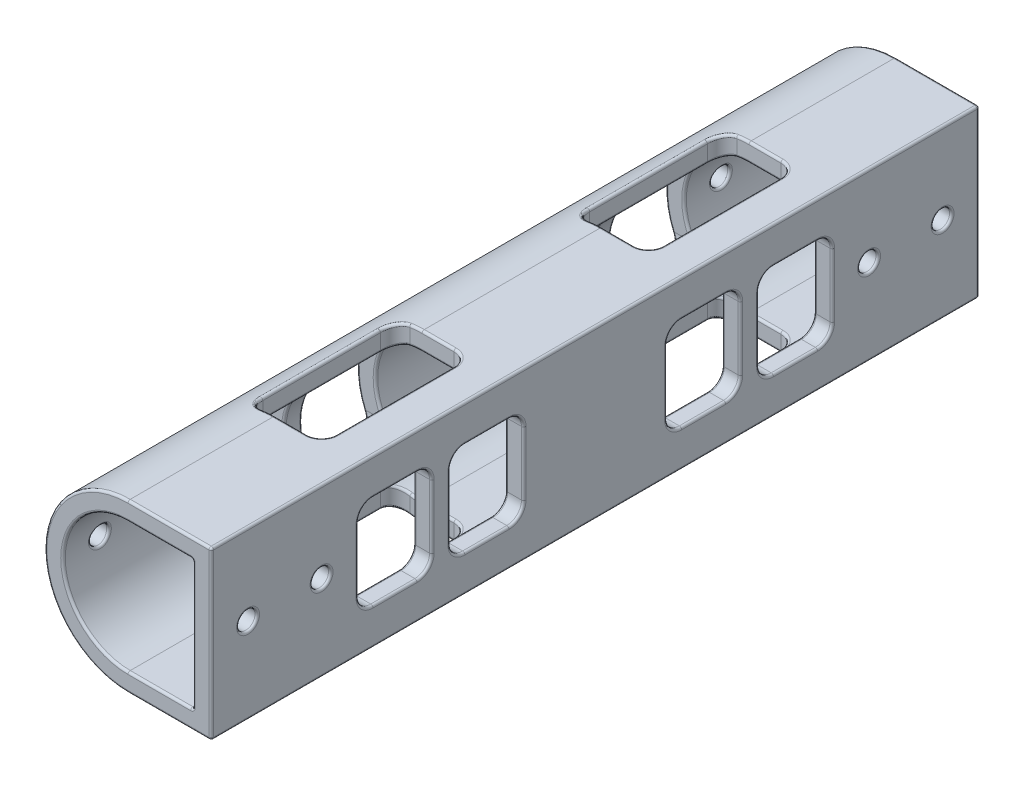
SolidWorks part; units mm, degrees
ref_plane "Front Plane" through (0, 0, 0) normal (0, 0, 1) x (1, 0, 0)
ref_plane "Top Plane" through (0, 0, 0) normal (0, 1, 0) x (1, 0, 0)
ref_plane "Right Plane" through (0, 0, 0) normal (1, 0, 0) x (0, 0, -1)
sketch "Sketch1" plane through (0, 0, 0) normal (0, 0, 1) x (1, 0, 0)
  line L1 (0, 13.9792) -> (14.3954, 13.9792)
  line L2 (0, 13.9792) -> (0, -14.8117)
  line L3 (0, -14.8117) -> (14.3955, -14.8117)
  line L4 (14.3954, 13.9792) -> (14.3955, -14.8117)
  line L5 (11.2204, -11.6367) -> (0, -11.6367)
  line L6 (11.2204, -11.6367) -> (11.2204, 10.8042)
  line L7 (11.2204, 10.8042) -> (0, 10.8042)
  line L8 (0, -11.6367) -> (0, 10.8042)
  arc A0 (0, -11.6367) -> (0, 10.8042) centre (0, -0.4163) cw
  arc A1 (0, 13.9792) -> (0, -14.8117) centre (0, -0.4163) ccw
  dimension "D1" = 28.7909
  dimension "D2" = 14.3954
  dimension "D3" = 3.175
  dimension "D4" = 3.175
  dimension "D5" = 3.175
extrude "Boss-Extrude1" add sketch "Sketch1" along normal blind 132.6829 contours L2 A1 A0 | L7 L6 L5 L2 L3 L4 L1 region at (7.1977, 13.6573, 0) region at (-0.3219, 12.3917, 0)
sketch "Sketch3" plane through (0, 0, 0) normal (1, 0, 0) x (0, 0, -1)
  line L6 (0, 13.9792) -> (0, -14.8117) construction
  line L11 (-132.6829, -11.6367) -> (0, -11.6367) construction
  line L12 (-104.7429, -8.4617) -> (-97.1229, -8.4617)
  line L13 (-107.2829, -5.9217) -> (-107.2829, 5.0892)
  line L14 (-104.7429, 7.6292) -> (-97.1229, 7.6292)
  line L15 (-94.5829, -5.9217) -> (-94.5829, 5.0892)
  line L17 (-132.6829, 10.8042) -> (0, 10.8042) construction
  line L18 (-132.6829, -11.6367) -> (-132.6829, 10.8042) construction
  line L22 (-88.8679, -8.4617) -> (-81.2479, -8.4617)
  line L23 (-91.4079, -5.9217) -> (-91.4079, 5.0892)
  line L24 (-88.8679, 7.6292) -> (-81.2479, 7.6292)
  line L25 (-78.7079, -5.9217) -> (-78.7079, 5.0892)
  line L26 (-35.56, -8.4617) -> (-27.94, -8.4617)
  line L27 (-38.1, -5.9217) -> (-38.1, 5.0892)
  line L28 (-35.56, 7.6292) -> (-27.94, 7.6292)
  line L29 (-25.4, -5.9217) -> (-25.4, 5.0892)
  line L31 (-51.435, -8.4617) -> (-43.815, -8.4617)
  line L32 (-53.975, -5.9217) -> (-53.975, 5.0892)
  line L33 (-51.435, 7.6292) -> (-43.815, 7.6292)
  line L34 (-41.275, -5.9217) -> (-41.275, 5.0892)
  arc A3 (-94.5829, 5.0892) -> (-97.1229, 7.6292) centre (-97.1229, 5.0892) ccw
  arc A4 (-97.1229, -8.4617) -> (-94.5829, -5.9217) centre (-97.1229, -5.9217) ccw
  arc A5 (-107.2829, -5.9217) -> (-104.7429, -8.4617) centre (-104.7429, -5.9217) ccw
  arc A6 (-107.2829, 5.0892) -> (-104.7429, 7.6292) centre (-104.7429, 5.0892) cw
  arc A7 (-38.1, 5.0892) -> (-35.56, 7.6292) centre (-35.56, 5.0892) cw
  arc A8 (-25.4, 5.0892) -> (-27.94, 7.6292) centre (-27.94, 5.0892) ccw
  arc A9 (-27.94, -8.4617) -> (-25.4, -5.9217) centre (-27.94, -5.9217) ccw
  arc A10 (-78.7079, -5.9217) -> (-81.2479, -8.4617) centre (-81.2479, -5.9217) cw
  arc A11 (-78.7079, 5.0892) -> (-81.2479, 7.6292) centre (-81.2479, 5.0892) ccw
  arc A12 (-91.4079, 5.0892) -> (-88.8679, 7.6292) centre (-88.8679, 5.0892) cw
  arc A13 (-91.4079, -5.9217) -> (-88.8679, -8.4617) centre (-88.8679, -5.9217) ccw
  arc A14 (-38.1, -5.9217) -> (-35.56, -8.4617) centre (-35.56, -5.9217) ccw
  arc A15 (-41.275, 5.0892) -> (-43.815, 7.6292) centre (-43.815, 5.0892) ccw
  arc A16 (-53.975, 5.0892) -> (-51.435, 7.6292) centre (-51.435, 5.0892) cw
  arc A17 (-51.435, -8.4617) -> (-53.975, -5.9217) centre (-51.435, -5.9217) cw
  arc A18 (-43.815, -8.4617) -> (-41.275, -5.9217) centre (-43.815, -5.9217) ccw
  point P28 (-94.5829, -0.4163)
  point P49 (-47.625, 7.6292)
  dimension "D2" = 3.175
  dimension "D4" = 12.7
  dimension "D5" = 2.54
  dimension "D14" = 2.54
  dimension "D15" = 2.54
  dimension "D20" = 2.54
  dimension "D1" = 3.175
  dimension "D3" = 25.4
  dimension "D6" = 25.4
  dimension "D7" = 12.7
  dimension "D8" = 3.175
  dimension "D9" = 12.7
  dimension "D10" = 3.175
  dimension "D11" = 3.175
  dimension "D12" = 3.175
  dimension "D13" = 3.175
  dimension "D16" = 12.7
  dimension "D17" = 3.175
  dimension "D18" = 3.175
  dimension "D19" = 3.175
extrude "Cut-Extrude1" cut sketch "Sketch3" against normal blind 25.4 and the other way blind 25.4
sketch "Sketch6" plane through (0, 0, 0) normal (0, 1, 0) x (1, 0, 0)
  line L5 (0, -132.6829) -> (14.3954, -132.6829) construction
  line L6 (-2.1145, -25.4) -> (5.5054, -25.4)
  line L11 (-4.6546, -27.94) -> (-4.6545, -48.26)
  line L12 (-2.1145, -50.8) -> (5.5054, -50.8)
  line L13 (8.0454, -27.94) -> (8.0455, -48.26)
  line L14 (5.5054, -107.2829) -> (-2.1145, -107.2829)
  line L15 (8.0454, -104.7429) -> (8.0454, -84.4229)
  line L16 (5.5054, -81.8829) -> (-2.1146, -81.8829)
  line L17 (-4.6546, -104.7429) -> (-4.6546, -84.4229)
  line L18 (11.2204, -132.6829) -> (11.2204, 0) construction
  line L19 (0, 0) -> (14.3954, 0) construction
  arc A0 (-2.1145, -107.2829) -> (-4.6546, -104.7429) centre (-2.1146, -104.7429) cw
  arc A1 (8.0454, -104.7429) -> (5.5054, -107.2829) centre (5.5054, -104.7429) cw
  arc A2 (-2.1146, -81.8829) -> (-4.6546, -84.4229) centre (-2.1146, -84.4229) ccw
  arc A3 (8.0454, -84.4229) -> (5.5054, -81.8829) centre (5.5054, -84.4229) ccw
  arc A4 (-2.1145, -50.8) -> (-4.6545, -48.26) centre (-2.1145, -48.26) cw
  arc A5 (5.5054, -50.8) -> (8.0455, -48.26) centre (5.5055, -48.26) ccw
  arc A6 (-2.1145, -25.4) -> (-4.6546, -27.94) centre (-2.1146, -27.94) ccw
  arc A7 (5.5054, -25.4) -> (8.0454, -27.94) centre (5.5054, -27.94) cw
  point P21 (8.0454, -107.2829)
  point P26 (8.0455, -81.8829)
  dimension "D7" = 2.54
  dimension "D1" = 25.4
  dimension "D2" = 25.4
  dimension "D3" = 3.175
  dimension "D4" = 12.7
  dimension "D5" = 25.4
  dimension "D6" = 25.4
extrude "Cut-Extrude2" cut sketch "Sketch6" against normal blind 25.4 and the other way blind 25.4
sketch "Sketch7" plane through (0, 0, 0) normal (1, 0, 0) x (0, 0, -1)
  line L0 (-132.6829, 0) -> (0, 0) construction
  line L2 (-132.6829, 13.9792) -> (-132.6829, -14.8117) construction
  line L3 (-66.3414, -21.0207) -> (-66.3414, 21.0207)
  line L6 (0, 13.9792) -> (0, -14.8117) construction
  circle A0 centre (-126.3329, 0) radius 1.5875
  circle A1 centre (-113.6329, 0) radius 1.5875
  circle A2 centre (-19.05, 0) radius 1.5875
  circle A3 centre (-6.35, 0) radius 1.5875
  point P3 (-111.5194, 0)
  point P12 (-66.3414, 0)
  point P13 (-66.3414, 0)
  dimension "D2" = 3.175
  dimension "D1" = 6.35
  dimension "D3" = 12.7
  dimension "D4" = 6.35
extrude "Cut-Extrude3" cut sketch "Sketch7" against normal blind 25.4 and the other way blind 25.4 contours A3 | A2 | A1 | A0
fillet "Fillet3" radius 0.3969 242 edges at (2.7527, -14.8117, 25.4) (-1.0602, -14.7726, 25.4) (-0.3066, -14.8084, 29.7241) (-4.6546, -14.0384, 38.1) (2.7527, -14.8117, 81.8829) (-1.0602, -14.7726, 81.8829) (-0.3066, -14.8084, 86.207) (-4.6546, -14.0384, 94.5829) (-7.8211, 7.6292, 31.75) (-8.9167, 6.3948, 25.7612) (-11.2204, -0.4163, 25.4) (-7.8211, 7.6292, 85.0579) (-8.9167, 6.3948, 79.0691) (-11.2204, -0.4163, 78.7079) (-7.8211, 7.6292, 47.625) (-8.9167, 6.3948, 41.6362) (-11.2204, -0.4163, 41.275) (-7.8211, 7.6292, 100.9329) (-8.9167, 6.3948, 94.9441) (-11.2204, -0.4163, 94.5829) (5.6102, 10.8042, 132.6829) (7.1977, -14.8117, 132.6829) (14.3954, -0.4163, 25.4) (14.3954, 6.8852, 26.1439) (14.3954, 7.6292, 31.75) (14.3954, -0.4163, 78.7079) (14.3954, 6.8852, 79.4518) (14.3954, 7.6292, 85.0579) (14.3954, -0.4163, 41.275) (14.3954, 6.8852, 42.0189) (14.3954, 7.6292, 47.625) (14.3954, -0.4163, 94.5829) (14.3954, 6.8852, 95.3268) (14.3954, 7.6292, 100.9329) (2.7527, 10.8042, 25.4) (-1.062, 10.7538, 25.4) (-0.2928, 10.8004, 29.71) (-4.6546, 9.7932, 38.1) (-4.6546, -10.6257, 38.1) (2.7527, 10.8042, 81.8829) (-1.062, 10.7538, 81.8829) (-0.2928, 10.8004, 86.1929) (-4.6546, 9.7932, 94.5829) (-4.6546, -10.6257, 94.5829) (14.3954, 1.5875, 126.3329) (11.2204, 0, 127.9204) (-11.1606, 0.7412, 124.9291) (-14.3873, 0.067, 124.7468) (14.3954, 1.5875, 113.6329) (11.2204, 0, 115.2204) (-11.1606, 0.7412, 112.2291) (-14.3873, 0.067, 112.0468) (14.3954, 1.5875, 19.05) (11.2204, 0, 20.6375) (-11.2096, 0.0763, 17.4643) (-14.3483, 0.7476, 17.6495) (14.3954, 1.5875, 6.35) (11.2204, 0, 7.9375) (-11.2096, 0.0763, 4.7643) (-14.3483, 0.7476, 4.9495) (-1.062, -11.5863, 25.4) (2.7527, 13.9792, 25.4) (-1.0602, 13.9401, 25.4) (7.3015, 10.8042, 26.1439) (7.3015, -14.8117, 26.1439) (7.3015, 13.9792, 26.1439) (8.0455, 10.8042, 38.1) (8.0455, -14.8117, 38.1) (8.0455, 13.9792, 38.1) (7.3015, 10.8042, 50.0561) (7.3015, -14.8117, 50.0561) (7.3015, 13.9792, 50.0561) (-1.062, -11.5863, 50.8) (2.7527, 10.8042, 50.8) (-1.062, 10.7538, 50.8) (2.7527, -14.8117, 50.8) (-1.0602, -14.7726, 50.8) (2.7527, 13.9792, 50.8) (-1.0602, 13.9401, 50.8) (-1.062, -11.5863, 81.8829) (2.7527, 13.9792, 81.8829) (-1.0602, 13.9401, 81.8829) (7.3015, 10.8042, 82.6268) (7.3015, -14.8117, 82.6268) (7.3015, 13.9792, 82.6268) (8.0454, 10.8042, 94.5829) (8.0454, -14.8117, 94.5829) (8.0454, 13.9792, 94.5829) (7.3015, 10.8042, 106.5389) (7.3015, -14.8117, 106.5389) (7.3015, 13.9792, 106.5389) (-1.062, -11.5863, 107.2829) (2.7527, 10.8042, 107.2829) (-1.062, 10.7538, 107.2829) (2.7527, -14.8117, 107.2829) (-1.0602, -14.7726, 107.2829) (2.7527, 13.9792, 107.2829) (-1.0602, 13.9401, 107.2829) (-4.6546, 13.2059, 38.1) (-0.1347, 13.9786, 29.5311) (-3.4241, -14.3985, 50.4364) (-3.9397, 13.4296, 50.0265) (-4.6546, 13.2059, 94.5829) (-3.7118, 13.4924, 82.4479) (-3.4241, -14.3985, 106.9193) (-3.9397, 13.4296, 106.5093) (11.2204, 7.6292, 31.75) (-11.9373, 7.6292, 31.75) (11.2204, 6.8852, 26.1439) (-12.3169, 7.0351, 26.3075) (11.2204, -0.4163, 25.4) (-14.3954, -0.4163, 25.4) (11.2204, -7.7178, 26.1439) (-8.1547, -8.1234, 26.6734) (-12.4616, -7.6231, 26.054) (11.2204, -8.4617, 31.75) (-7.8211, -8.4617, 31.75) (-11.9373, -8.4617, 31.75) (11.2204, -7.7178, 37.3561) (-8.4657, -7.7804, 37.2911) (-12.1897, -8.0739, 36.9089) (11.2204, -0.4163, 38.1) (-11.2204, -0.4163, 38.1) (-14.3954, -0.4163, 38.1) (11.2204, 6.8852, 37.3561) (-10.584, 3.309, 33.7482) (-13.9576, 3.107, 33.9717) (11.2204, -8.4617, 85.0579) (-7.8211, -8.4617, 85.0579) (-11.9373, -8.4617, 85.0579) (11.2204, -7.7178, 90.6639) (-8.4657, -7.7804, 90.599) (-13.9064, -4.1365, 87.0611) (11.2204, -0.4163, 91.4079) (-11.2204, -0.4163, 91.4079) (-14.3954, -0.4163, 91.4079) (11.2204, 6.8852, 90.6639) (-10.584, 3.309, 87.0561) (-12.4616, 6.7906, 90.7538) (11.2204, 7.6292, 85.0579) (-11.9373, 7.6292, 85.0579) (11.2204, 6.8852, 79.4518) (-12.3169, 7.0351, 79.6154) (11.2204, -0.4163, 78.7079) (-14.3954, -0.4163, 78.7079) (11.2204, -7.7178, 79.4518) (-8.2858, -7.9822, 79.7626) (-12.6651, -7.259, 79.0884) (11.2204, -0.4163, 41.275) (-14.3954, -0.4163, 41.275) (11.2204, -7.7178, 42.0189) (-8.1547, -8.1234, 42.5484) (-12.4616, -7.6231, 41.929) (11.2204, -8.4617, 47.625) (-7.8211, -8.4617, 47.625) (-11.9373, -8.4617, 47.625) (11.2204, -7.7178, 53.2311) (-8.4657, -7.7804, 53.1661) (-13.9064, -4.1365, 49.6282) (11.2204, -0.4163, 53.975) (-11.2204, -0.4163, 53.975) (-14.3954, -0.4163, 53.975) (11.2204, 6.8852, 53.2311) (-8.4, 7.0228, 53.0821) (-12.4616, 6.7906, 53.321) (11.2204, 7.6292, 47.625) (-11.9373, 7.6292, 47.625) (11.2204, 6.8852, 42.0189) (-12.3169, 7.0351, 42.1825) (11.2204, -0.4163, 94.5829) (-14.3954, -0.4163, 94.5829) (11.2204, -7.7178, 95.3268) (-8.2858, -7.9822, 95.6376) (-12.6651, -7.259, 94.9634) (11.2204, -8.4617, 100.9329) (-7.8211, -8.4617, 100.9329) (-11.9373, -8.4617, 100.9329) (11.2204, -7.7178, 106.5389) (-8.4657, -7.7804, 106.474) (-13.9064, -4.1365, 102.9361) (11.2204, -0.4163, 107.2829) (-11.2204, -0.4163, 107.2829) (-14.3954, -0.4163, 107.2829) (11.2204, 6.8852, 106.5389) (-8.4, 7.0228, 106.3899) (-12.4616, 6.7906, 106.6288) (11.2204, 7.6292, 100.9329) (-11.9373, 7.6292, 100.9329) (11.2204, 6.8852, 95.3268) (-12.3169, 7.0351, 95.4904) (-11.2204, -0.4163, 0) (5.6102, 10.8042, 0) (11.2204, -0.4163, 0) (5.6102, -11.6367, 0) (7.1977, 13.9792, 0) (-14.3954, -0.4163, 0) (7.1977, -14.8117, 0) (14.3954, -0.4163, 0) (-11.2204, -0.4163, 132.6829) (11.2204, -0.4163, 132.6829) (5.6102, -11.6367, 132.6829) (7.1977, 13.9792, 132.6829) (-14.3954, -0.4163, 132.6829) (11.2204, -11.6367, 66.3414) (11.2204, 10.8042, 66.3414) (14.3954, 13.9792, 66.3414) (14.3954, -7.7178, 26.1439) (14.3955, -8.4617, 31.75) (14.3955, -7.7178, 37.3561) (14.3954, -0.4163, 38.1) (14.3954, 6.8852, 37.3561) (14.3955, -8.4617, 85.0579) (14.3955, -7.7178, 90.6639) (14.3954, -0.4163, 91.4079) (14.3954, 6.8852, 90.6639) (14.3954, -7.7178, 79.4518) (14.3954, -7.7178, 42.0189) (14.3955, -8.4617, 47.625) (14.3955, -7.7178, 53.2311) (14.3954, -0.4163, 53.975) (14.3954, 6.8852, 53.2311) (14.3954, -7.7178, 95.3268) (14.3955, -8.4617, 100.9329) (14.3955, -7.7178, 106.5389) (14.3954, -0.4163, 107.2829) (14.3954, 6.8852, 106.5389) (2.7527, -11.6367, 25.4) (7.3015, -11.6367, 26.1439) (8.0455, -11.6367, 38.1) (7.3015, -11.6367, 50.0561) (2.7527, -11.6367, 50.8) (2.7527, -11.6367, 81.8829) (7.3015, -11.6367, 82.6268) (8.0454, -11.6367, 94.5829) (7.3015, -11.6367, 106.5389) (2.7527, -11.6367, 107.2829) (-3.3843, 10.2816, 50.4599) (-3.7175, -11.003, 25.9697) (-3.966, -10.9124, 49.9989) (-3.3843, 10.2816, 106.9427) (-3.7175, -11.003, 82.4525) (-3.966, -10.9124, 106.4818)
fillet "Fillet4" radius 0.3969 5 edges at (14.2792, 13.863, 132.5666) (14.2792, -14.6955, 0.1162) (14.3955, -14.8117, 66.3414) (14.3955, -14.6955, 132.5666) (14.3954, -0.4163, 132.6829)
